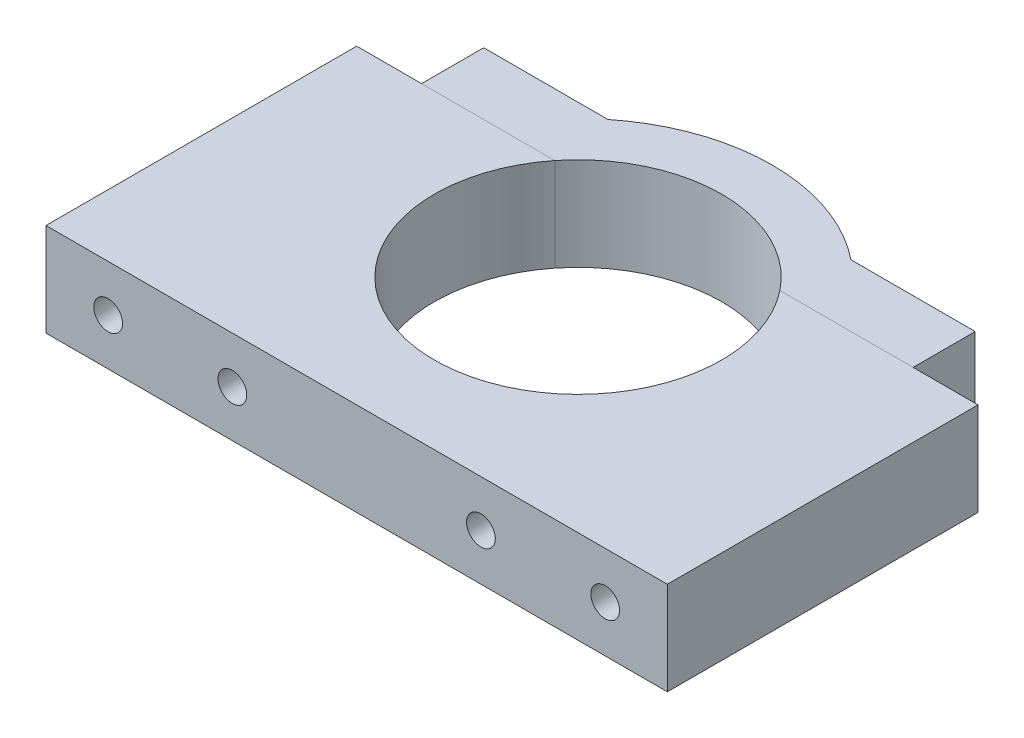
SolidWorks part; units mm, degrees
ref_plane "前视基准面" through (0, 0, 0) normal (0, 0, 1) x (1, 0, 0)
ref_plane "上视基准面" through (0, 0, 0) normal (0, 1, 0) x (1, 0, 0)
ref_plane "右视基准面" through (0, 0, 0) normal (1, 0, 0) x (0, 0, -1)
sketch "草图1" plane through (0, 0, 0) normal (0, 1, 0) x (1, 0, 0)
  line L0 (-79.4192, 0) -> (86.8155, 0) construction
  line L1 (0, 43.3474) -> (0, -42.343) construction
  line L2 (-40, -28.5) -> (40, -28.5)
  line L3 (40, -28.5) -> (40, 11.5)
  line L4 (40, 11.5) -> (14.4914, 11.5)
  line L5 (31.6445, 11.5) -> (31.6445, 19.5)
  line L6 (31.6445, 19.5) -> (15.6445, 19.5)
  line L7 (-31.6445, 19.5) -> (-15.6445, 19.5)
  line L8 (-31.6445, 11.5) -> (-31.6445, 19.5)
  line L9 (-40, 11.5) -> (-14.4914, 11.5)
  line L10 (-40, -28.5) -> (-40, 11.5)
  circle A0 centre (0, 0) radius 18.5
  arc A1 (15.6445, 19.5) -> (-15.6445, 19.5) centre (0, 0) ccw
  point P20 (0, -28.5)
  dimension "D1" = 18.5
  dimension "D2" = 25
  dimension "D3" = 40
  dimension "D5" = 40
  dimension "D6" = 8
  dimension "D7" = 16
extrude "motor Mount" add sketch "草图1" along normal mid plane 12 contours A0 L9 L10 L2 L3 L4 region at (-39.1056, 0, 8.5)
extrude "tapping cover" add sketch "草图1<4>" along normal mid plane 12 separate body contours L6 A1 L7 L8 L9 A0 L4 L5 region at (-30.9974, 0, -15.5)
sketch "草图1<4>" plane through (0, 0, 0) normal (0, 1, 0) x (1, 0, 0) same geometry as "草图1"
sketch "草图2" plane through (0, 0, 28.5) normal (0, 0, 1) x (1, 0, 0)
  line L0 (-43.3546, 0) -> (46.0848, 0) construction
  line L1 (0, 17.0876) -> (0, -23.3955) construction
  circle A0 centre (32, 0) radius 1.85
  circle A1 centre (16, 0) radius 1.85
  circle A2 centre (-16, 0) radius 1.85
  circle A3 centre (-32, 0) radius 1.85
  dimension "D1" = 3.7
  dimension "D2" = 3.7
  dimension "D4" = 16
  dimension "D3" = 16
extrude "tapping holes_bottom" cut sketch "草图2" against normal blind 8
